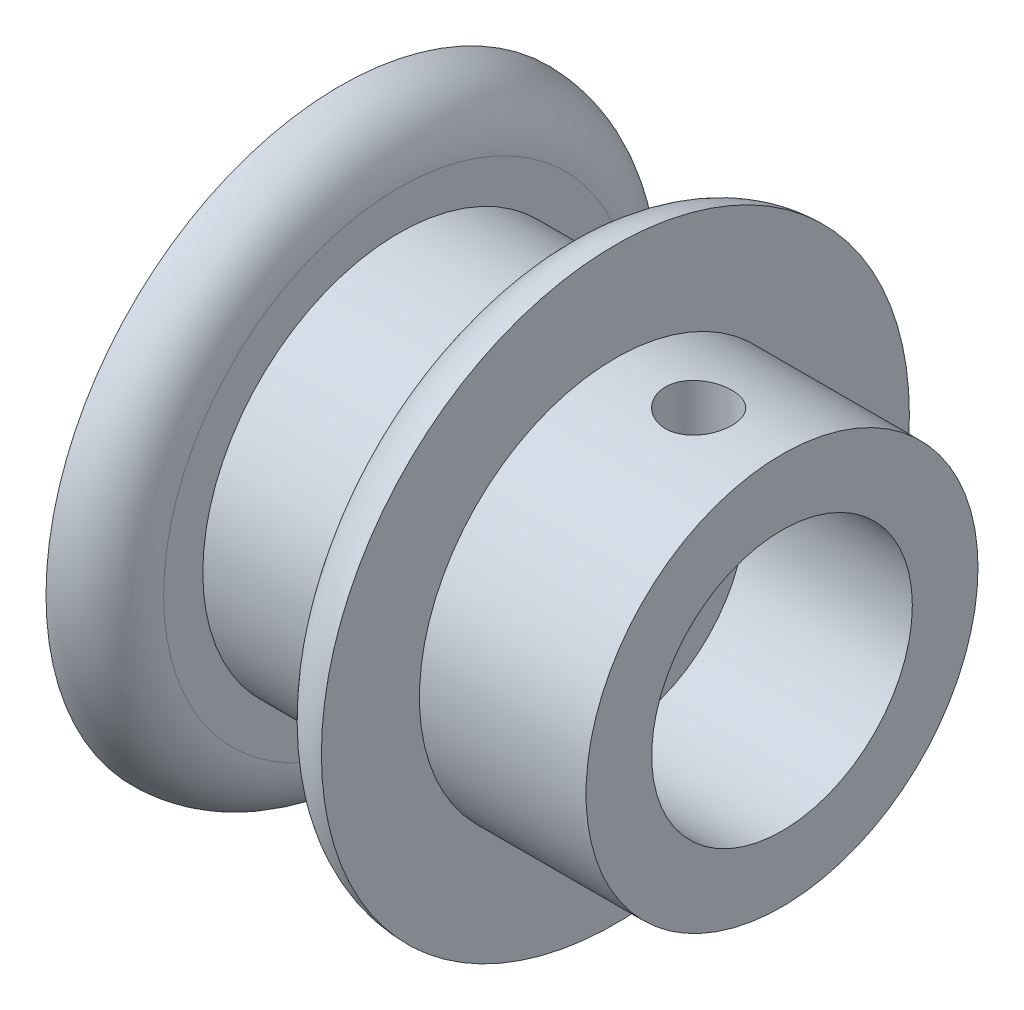
SolidWorks part; units mm, degrees
ref_plane "Front Plane" through (0, 0, 0) normal (0, 0, 1) x (1, 0, 0)
ref_plane "Top Plane" through (0, 0, 0) normal (0, 1, 0) x (1, 0, 0)
ref_plane "Right Plane" through (0, 0, 0) normal (1, 0, 0) x (0, 0, -1)
sketch "Эскиз1" plane through (0, 0, 0) normal (1, 0, 0) x (0, 0, -1)
  line L0 (-10, 0) -> (10, 0)
  circle A0 centre (0, 0) radius 6.6
  circle A1 centre (0, 0) radius 10
extrude "Бобышка-Вытянуть3" add sketch "Эскиз1" along normal blind 14.35 contours L0 A1 A0 region at (0, 6.8236, 0)
sketch "Эскиз3" plane through (14.35, 0, 0) normal (1, 0, 0) x (0, 0, -1)
  line L0 (-15, 0) -> (15, 0)
  circle A0 centre (0, 0) radius 6.6
  circle A1 centre (0, 0) radius 3.2
  circle A2 centre (0, 0) radius 10
  circle A3 centre (0, 0) radius 15
  arc M4 (10, 0) -> (-10, 0) centre (0, 0) ccw
  arc M6 (-6.6, 0) -> (6.6, 0) centre (0, 0) cw
extrude "Бобышка-Вытянуть7" add sketch "Эскиз3" against normal blind 3 contours L0 A3 M4 | A1 L0 M6 region at (14.35, 14.6646, 0) region at (14.35, 3.2446, 0)
sketch "Эскиз5" plane through (0, 0, 0) normal (-1, 0, 0) x (0, 0, 1)
  line L0 (-15, 0) -> (15, 0)
  circle A0 centre (0, 0) radius 3.2
  circle A1 centre (0, 0) radius 15
  arc M2 (-6.6, 0) -> (6.6, 0) centre (0, 0) cw
  arc M4 (10, 0) -> (-10, 0) centre (0, 0) ccw
extrude "Бобышка-Вытянуть8" add sketch "Эскиз5" against normal blind 3 contours L0 A1 M4 | A0 L0 M2 region at (0, 14.6646, 0) region at (0, 3.2446, 0)
sketch "Эскиз6" plane through (0, 0, 0) normal (-1, 0, 0) x (0, 0, 1)
  line L0 (0, 0) -> (0, 3)
  line L1 (0, 3) -> (-6.6, 3)
  line L2 (-6.6, 3) -> (-14.6969, 3)
  line L3 (-14.6969, 3) -> (-14.6969, -3)
  line L4 (0, 3) -> (14.6969, 3)
  line L5 (14.6969, 3) -> (14.6969, -3)
  line L6 (14.6969, -3) -> (-14.6969, -3)
  circle A0 centre (0, 0) radius 6.6
  arc A1 (15, 0) -> (-15, 0) centre (0, 0) ccw construction
  line M9 (-15, 0) -> (-3.2, 0)
  arc M10 (-3.2, 0) -> (3.2, 0) centre (0, 0) cw
  line M11 (3.2, 0) -> (15, 0)
extrude "Бобышка-Вытянуть9" add sketch "Эскиз6" along normal blind 10 contours A0 L1 L2 L3 M9 | L1 A0 M9 M10 | L4 A0 L1 M10 | A0 L4 M11 M10 | A0 L5 L4 M11 region at (0, 1.5752, -4.4616) region at (0, 4.494, 0) region at (0, 1.5752, 4.4616) region at (0, 1.5214, -10.5283) region at (0, 1.5214, 10.5283)
sketch "Эскиз7" plane through (14.35, 0, 0) normal (1, 0, 0) x (0, 0, -1)
  line L0 (14.6969, 0) -> (14.6969, 3)
  line L1 (14.6969, 3) -> (5.8788, 3)
  line L2 (-5.8788, 3) -> (-14.6969, 3)
  line L3 (-14.6969, 3) -> (-14.6969, 0)
  line L4 (-14.6969, 0) -> (-3.2, 0)
  line L5 (3.2, 0) -> (14.6969, 0)
  arc A0 (-3.2, 0) -> (3.2, 0) centre (0, 0) cw
  circle A1 centre (0, 0) radius 6.6
  line M1 (3.2, 0) -> (15, 0)
  line M3 (-15, 0) -> (-3.2, 0)
  arc M4 (-3.2, 0) -> (3.2, 0) centre (0, 0) cw
extrude "Бобышка-Вытянуть10" add sketch "Эскиз7" along normal blind 10 contours A1 L5 L0 L1 | A1 L4 M1 M4 | A1 L2 L3 M3 region at (14.35, 1.5214, -10.5283) region at (14.35, 3.2446, 0) region at (14.35, 1.5214, 10.5283)
sketch "Эскиз8" plane through (0, 3, 0) normal (0, 1, 0) x (1, 0, 0)
  line L0 (-5, 5.8788) -> (-5, 14.6969)
  line L1 (-10, 5.8788) -> (0, 5.8788) construction
  line L2 (-10, 14.6969) -> (0, 14.6969) construction
  line L3 (-5, -5.8788) -> (-5, -14.6969)
  line L4 (-10, -5.8788) -> (0, -5.8788) construction
  line L5 (-10, -14.6969) -> (0, -14.6969) construction
  line L6 (19.35, -5.8788) -> (19.35, -14.6969)
  line L7 (24.35, -5.8788) -> (14.35, -5.8788) construction
  line L8 (24.35, -14.6969) -> (14.35, -14.6969) construction
  line L9 (19.35, 14.6969) -> (19.35, 5.8788)
  line L10 (24.35, 14.6969) -> (14.35, 14.6969) construction
  line L11 (24.35, 5.8788) -> (14.35, 5.8788) construction
  circle A0 centre (-5, 10.2879) radius 1.7
  circle A1 centre (19.35, 10.2879) radius 1.7
  circle A2 centre (19.35, -10.2879) radius 1.7
  circle A3 centre (-5, -10.2879) radius 1.7
extrude "Вырез-Вытянуть1" cut sketch "Эскиз8" against normal blind 10 contours L0 A0 | L0 A0 | L9 A1 | L9 A1 | L6 A2 | L6 A2 | L3 A3 | L3 A3 region at (-5.7215, 3, -10.2879) region at (-4.2785, 3, -10.2879) region at (-4.2785, 3, 10.2879) region at (-5.7215, 3, 10.2879) region at (20.0715, 3, 10.2879) region at (18.6285, 3, 10.2879) region at (20.0715, 3, -10.2879) region at (18.6285, 3, -10.2879)
sketch "Эскиз9" plane through (0, 0, 0) normal (0, -1, 0) x (1, 0, 0)
  line L0 (7.175, 6.6) -> (7.175, -6.6)
  line L1 (11.35, 6.6) -> (3, 6.6) construction
  line L2 (11.35, -6.6) -> (3, -6.6) construction
  circle A0 centre (7.175, 0) radius 1.7
extrude "Вырез-Вытянуть2" cut sketch "Эскиз9" against normal blind 14 contours L0 A0 | L0 A0 region at (7.8965, 0, 0) region at (6.4535, 0, 0)
fillet "Скругление1" radius 5 4 edges at (24.35, 1.5, 14.6969) (-10, 1.5, 14.6969) (-10, 1.5, -14.6969) (24.35, 1.5, -14.6969)
sketch "Эскиз10" plane through (0, 0, 0) normal (0, -1, 0) x (1, 0, 0)
  line L0 (0, 15) -> (0, -15)
  line L1 (0, -15) -> (-10.3547, -15)
  line L2 (-10.3547, -15) -> (-10.3547, 15)
  line L3 (-10.3547, 15) -> (0, 15)
  line L4 (14.35, 15) -> (14.35, -15)
  line L5 (14.35, -15) -> (25.2486, -15)
  line L6 (25.2486, -15) -> (25.2486, 15)
  line L7 (25.2486, 15) -> (14.35, 15)
extrude "Вырез-Вытянуть3" cut sketch "Эскиз10" against normal blind 14
sketch "Эскиз11" plane through (14.35, 0, 0) normal (1, 0, 0) x (0, 0, -1)
  circle A0 centre (0, 0) radius 6.6
extrude "Вырез-Вытянуть4" cut sketch "Эскиз11" against normal up to surface (11.35 mm away) up to face at (3, 2.45, 0)
sketch "Эскиз12" plane through (14.35, 0, 0) normal (1, 0, 0) x (0, 0, -1)
  circle A0 centre (0, 0) radius 6.6
  circle A1 centre (0, 0) radius 10
extrude "Бобышка-Вытянуть11" add sketch "Эскиз12" against normal up to surface (14.35 mm away) up to face at (0, 4.55, 0)
sketch "Эскиз13" plane through (14.35, 0, 0) normal (1, 0, 0) x (0, 0, -1)
  circle A0 centre (0, 0) radius 10
  circle A1 centre (0, 0) radius 15
extrude "Бобышка-Вытянуть12" add sketch "Эскиз13" against normal blind 3
sketch "Эскиз14" plane through (0, 0, 0) normal (-1, 0, 0) x (0, 0, 1)
  circle A0 centre (0, 0) radius 3.2
  circle A1 centre (0, 0) radius 15
extrude "Бобышка-Вытянуть13" add sketch "Эскиз14" against normal blind 3
sketch "Эскиз17" plane through (14.35, 0, 0) normal (1, 0, 0) x (0, 0, -1)
  circle A0 centre (0, 0) radius 15
  circle A1 centre (0, 0) radius 6.6
extrude "Вырез-Вытянуть5" cut sketch "Эскиз17" against normal blind 0.3 contours A0
sketch "Эскиз18" plane through (11.35, 0, 0) normal (-1, 0, 0) x (0, 0, 1)
  circle A0 centre (0, 0) radius 10
  circle A1 centre (0, 0) radius 15
extrude "Бобышка-Вытянуть14" add sketch "Эскиз18" along normal blind 0.3
sketch "Эскиз19" plane through (0, 0, 0) normal (0, 1, 0) x (1, 0, 0)
  line L0 (3, 0) -> (11.05, 0)
  line L1 (3, -15) -> (3, 15) construction
  line L2 (11.05, 10) -> (11.05, -10) construction
  circle A0 centre (7.025, 0) radius 1.7
extrude "Вырез-Вытянуть6" cut sketch "Эскиз19" along normal blind 19.3 contours L0 A0 | L0 A0 region at (7.025, 0, -0.7215) region at (7.025, 0, 0.7215)
sketch "Эскиз20" plane through (3, 0, 0) normal (1, 0, 0) x (0, 0, -1)
  circle A0 centre (0, 0) radius 3.2
  circle A1 centre (0, 0) radius 10
extrude "Бобышка-Вытянуть15" add sketch "Эскиз20" along normal up to surface (11.05 mm away) up to face at (14.05, 0, -6.6)
sketch "Эскиз21" plane through (14.05, 0, 0) normal (1, 0, 0) x (0, 0, -1)
  circle A0 centre (0, 0) radius 6.6
  circle A1 centre (0, 0) radius 10
extrude "Бобышка-Вытянуть16" add sketch "Эскиз21" along normal blind 8.5 contours A1 | A0
sketch "Эскиз22" plane through (0, 0, 0) normal (0, 1, 0) x (1, 0, 0)
  line L0 (22.55, 0) -> (14.05, 0)
  line L1 (22.55, -10) -> (22.55, 10) construction
  line L2 (14.05, -15) -> (14.05, 15) construction
  circle A0 centre (18.3, 0) radius 1.7
extrude "Вырез-Вытянуть7" cut sketch "Эскиз22" along normal blind 13.5 contours L0 A0 | L0 A0 region at (18.3, 0, 0.7215) region at (18.3, 0, -0.7215)
fillet "Скругление2" radius 3 2 edges at (11.05, 0, 15) (3, 0, 15)
sketch "Эскиз23" plane through (0, 0, 0) normal (0, 1, 0) x (1, 0, 0)
  line L0 (0, 0) -> (14.05, 0)
  line L1 (14.05, -10) -> (14.05, 10) construction
  line L2 (7.025, 10) -> (7.025, 7)
  line L3 (11.05, 10) -> (3, 10) construction
  circle A0 centre (7.025, 7) radius 0.75
extrude "Вырез-Вытянуть9" cut sketch "Эскиз23" against normal blind 10 and the other way blind 10 contours A0 region at (6.5097, 0, -6.4847)
sketch "Эскиз25" plane through (22.55, 0, 0) normal (1, 0, 0) x (0, 0, -1)
  circle A2 centre (0, 0) radius 6.65
extrude "Вырез-Вытянуть10" cut sketch "Эскиз25" against normal up to surface (8.5 mm away) up to face at (14.05, 0, -3.2)
